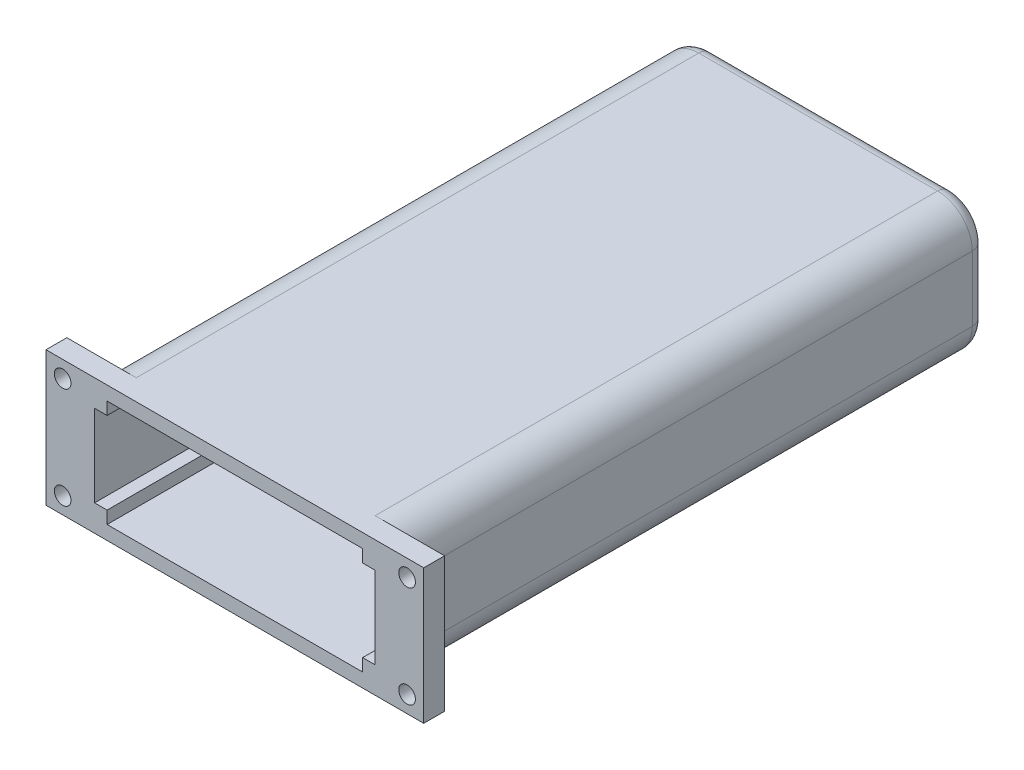
SolidWorks part; units mm, degrees
ref_plane "前视基准面" through (0, 0, 0) normal (0, 0, 1) x (1, 0, 0)
ref_plane "上视基准面" through (0, 0, 0) normal (0, 1, 0) x (1, 0, 0)
ref_plane "右视基准面" through (0, 0, 0) normal (1, 0, 0) x (0, 0, -1)
other "Configuration Table"
sketch "草图1" plane through (0, 0, 0) normal (0, 0, 1) x (1, 0, 0)
  line L0 (-9, 6.2) -> (-9, -5.6)
  line L5 (-11, 10) -> (33.4, 10)
  line L6 (-11, 10) -> (-11, -9.4)
  line L7 (-11, -9.4) -> (33.4, -9.4)
  line L8 (33.4, 10) -> (33.4, -9.4)
  line L9 (-9, -5.6) -> (-7.2, -5.6)
  line L10 (-7.2, -5.6) -> (-7.2, -7.4)
  line L11 (-7.2, -7.4) -> (29.6, -7.4)
  line L12 (29.6, -7.4) -> (29.6, -5.6)
  line L13 (29.6, -5.6) -> (31.4, -5.6)
  line L14 (31.4, -5.6) -> (31.4, 6.2)
  line L15 (31.4, 6.2) -> (29.6, 6.2)
  line L16 (29.6, 6.2) -> (29.6, 8)
  line L17 (29.6, 8) -> (-7.2, 8)
  line L18 (-7.2, 8) -> (-7.2, 6.2)
  line L19 (-7.2, 6.2) -> (-9, 6.2)
  dimension "D1" = 2
  dimension "D2" = 2
  dimension "D3" = 2
  dimension "D4" = 2
  dimension "D5" = 1.8
  dimension "D6" = 1.8
  dimension "D7" = 1.8
  dimension "D8" = 1.8
  dimension "D9" = 1.8
  dimension "D10" = 1.8
  dimension "D11" = 1.8
  dimension "D12" = 1.8
  dimension "D13" = 8
  dimension "D14" = 9
  dimension "D15" = 44.4
  dimension "D16" = 19.4
extrude "凸台-拉伸1" add sketch "草图1" along normal blind 83
fillet "圆角6" radius 5 1 edges at (-11, -9.4, 41.5)
fillet "圆角7" radius 5 1 edges at (-11, 10, 41.5)
fillet "圆角8" radius 5 1 edges at (33.4, 10, 41.5)
fillet "圆角9" radius 5 1 edges at (33.4, -9.4, 41.5)
fillet "圆角11" radius 2 8 edges at (-9.5355, -7.9355, 0) (-11, 0.3, 0) (-9.5355, 8.5355, 0) (11.2, 10, 0) (31.9355, 8.5355, 0) (33.4, 0.3, 0) (31.9355, -7.9355, 0) (11.2, -9.4, 0)
sketch "草图2" plane through (0, 0, 0) normal (0, 0, -1) x (-1, 0, 0)
  line L0 (-31.4, 6.2) -> (-31.4, -5.6)
  line L1 (-31.4, -5.6) -> (-29.6, -5.6)
  line L2 (-29.6, -5.6) -> (-29.6, -7.4)
  line L3 (-29.6, -7.4) -> (7.2, -7.4)
  line L4 (7.2, -7.4) -> (7.2, -5.6)
  line L5 (7.2, -5.6) -> (9, -5.6)
  line L6 (9, -5.6) -> (9, 6.2)
  line L7 (9, 6.2) -> (7.2, 6.2)
  line L8 (7.2, 6.2) -> (7.2, 8)
  line L9 (7.2, 8) -> (-29.6, 8)
  line L10 (-29.6, 8) -> (-29.6, 6.2)
  line L11 (-29.6, 6.2) -> (-31.4, 6.2)
extrude "凸台-拉伸2" add sketch "草图2" against normal blind 3
sketch "草图3" plane through (0, 0, 83) normal (0, 0, 1) x (1, 0, 0)
  line L1 (-16, 10) -> (38.4, 10)
  line L2 (-16, 10) -> (-16, -9.4)
  line L3 (-16, -9.4) -> (38.4, -9.4)
  line L4 (38.4, 10) -> (38.4, -9.4)
  line L6 (-11, 5) -> (-11, -4.4) construction
  line L8 (28.4, 10) -> (-6, 10) construction
  line L9 (-6, -9.4) -> (28.4, -9.4) construction
  circle A0 centre (-13.6, 7.6) radius 1.2
  circle A1 centre (-13.6, -7) radius 1.2
  circle A2 centre (36, 7.6) radius 1.2
  circle A3 centre (36, -7) radius 1.2
  point P20 (37.4038, 7.2984)
  line M5 (-6, -9.4) -> (28.4, -9.4)
  arc M6 (28.4, -9.4) -> (33.4, -4.4) centre (28.4, -4.4) ccw
  line M7 (33.4, -4.4) -> (33.4, 5)
  arc M8 (33.4, 5) -> (28.4, 10) centre (28.4, 5) ccw
  line M9 (28.4, 10) -> (-6, 10)
  arc M10 (-6, 10) -> (-11, 5) centre (-6, 5) ccw
  line M11 (-11, 5) -> (-11, -4.4)
  arc M12 (-11, -4.4) -> (-6, -9.4) centre (-6, -4.4) ccw
  line M13 (-9, -5.6) -> (-9, 6.2)
  line M14 (-9, 6.2) -> (-7.2, 6.2)
  line M15 (-7.2, 6.2) -> (-7.2, 8)
  line M16 (-7.2, 8) -> (29.6, 8)
  line M17 (29.6, 8) -> (29.6, 6.2)
  line M18 (29.6, 6.2) -> (31.4, 6.2)
  line M19 (31.4, 6.2) -> (31.4, -5.6)
  line M20 (31.4, -5.6) -> (29.6, -5.6)
  line M21 (29.6, -5.6) -> (29.6, -7.4)
  line M22 (29.6, -7.4) -> (-7.2, -7.4)
  line M23 (-7.2, -7.4) -> (-7.2, -5.6)
  line M24 (-7.2, -5.6) -> (-9, -5.6)
  dimension "D5" = 2.4
  dimension "D8" = 2.4
  dimension "D11" = 2.4
  dimension "D14" = 2.4
  dimension "D1" = 2.4
  dimension "D2" = 54.4
  dimension "D3" = 5
  dimension "D4" = 2.4
  dimension "D6" = 2.4
  dimension "D7" = 2.4
  dimension "D9" = 2.4
  dimension "D10" = 2.4
  dimension "D12" = 2.4
  dimension "D13" = 2.4
extrude "凸台-拉伸3" add sketch "草图3" along normal blind 3 contours L2 L3 L1 A1 A0 M12 M11 M10 | L4 L1 L3 A3 A2 M8 M7 M6 | M12 M5 M6 M7 M8 M9 M10 M11 M24 M13 M14 M15 M16 M17 M18 M19 M20 M21 M22 M23 region at (-13.0976, 0.3, 83) region at (11.2, 9.5155, 83) region at (35.4976, 0.3, 83)
